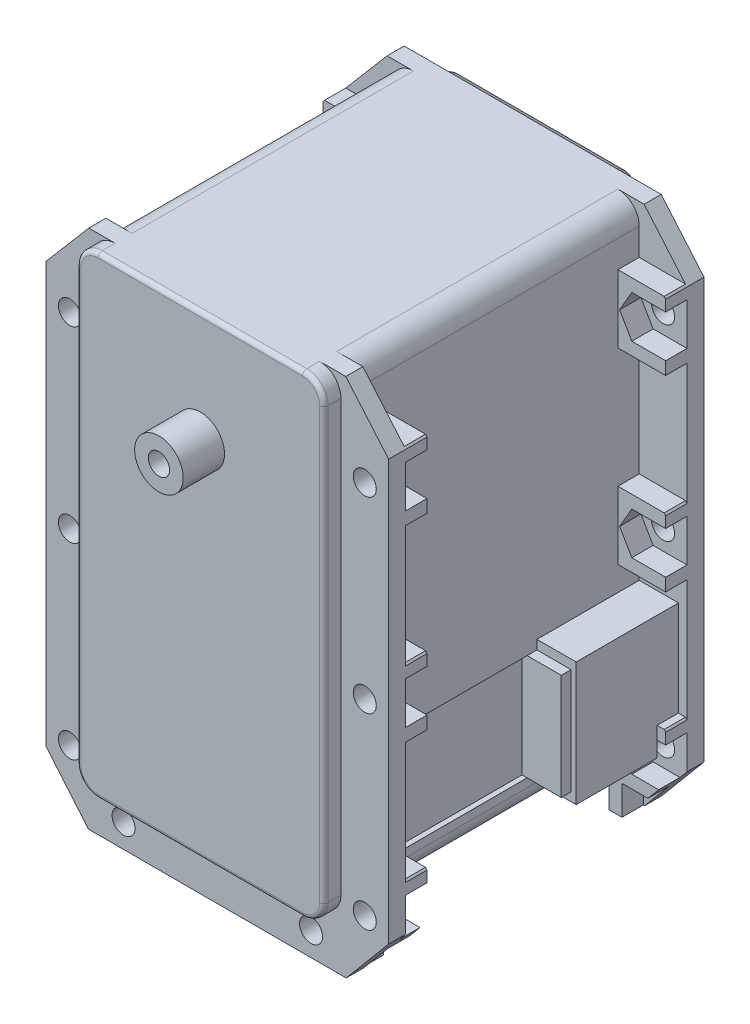
SolidWorks part; units mm, degrees
ref_plane "Ön Düzlem" through (0, 0, 0) normal (0, 0, 1) x (1, 0, 0)
ref_plane "Üst Düzlem" through (0, 0, 0) normal (0, 1, 0) x (1, 0, 0)
ref_plane "Sağ Düzlem" through (0, 0, 0) normal (1, 0, 0) x (0, 0, -1)
sketch "Sketch1" plane through (0, 0, 0) normal (0, 0, 1) x (1, 0, 0)
  line L1 (-14.5, 27.75) -> (14.5, 27.75)
  line L2 (-14.5, 27.75) -> (-14.5, -27.75)
  line L3 (-14.5, -27.75) -> (14.5, -27.75)
  line L4 (14.5, 27.75) -> (14.5, -27.75)
  line L5 (-14.5, 27.75) -> (14.5, -27.75) construction
  line L6 (-14.5, -27.75) -> (14.5, 27.75) construction
  point P0 (0, 0)
  dimension "D1" = 55.5
  dimension "D2" = 29
extrude "Boss-Extrude1" add sketch "Sketch1" along normal mid plane 41
ref_plane "Plane1" through (0, 0, 18.5) normal (0, 0, 1) x (1, 0, 0)
sketch "Sketch2" plane through (0, 0, 18.5) normal (0, 0, 1) x (1, 0, 0)
  line L1 (-15.0753, 27.75) -> (-20.1, 21.8536)
  line L2 (-20.1, 21.8536) -> (-20.1, -27.4155)
  line L3 (-20.1, -27.4155) -> (-15.1203, -33.35)
  line L4 (-15.1203, -33.35) -> (15.1203, -33.35)
  line L5 (15.1203, -33.35) -> (20.1, -27.4155)
  line L6 (20.1, -27.4155) -> (20.1, 21.8536)
  line L7 (20.1, 21.8536) -> (15.0753, 27.75)
  line L8 (15.0753, 27.75) -> (-15.0753, 27.75)
  line L9 (0, 0) -> (0, -33.35) construction
  line L10 (14.5, -27.75) -> (14.5, 27.75) construction
  line L11 (-14.5, -27.75) -> (14.5, -27.75) construction
  line L14 (14.5, 27.75) -> (-14.5, 27.75) construction
  circle A0 centre (17.3, 18.0845) radius 1.35
  circle A1 centre (17.3, -3.9155) radius 1.35
  circle A2 centre (17.3, -25.9155) radius 1.35
  circle A3 centre (11, -30.55) radius 1.35
  circle A4 centre (-11, -30.55) radius 1.35
  circle A5 centre (-17.3, -25.9155) radius 1.35
  circle A6 centre (-17.3, 18.0845) radius 1.35
  circle A7 centre (-17.3, -3.9155) radius 1.35
  dimension "D9" = 17.3
  dimension "D8" = 2.7
  dimension "D1" = 40.2
  dimension "D2" = 220
  dimension "D3" = 5.9345
  dimension "D4" = 5.6
  dimension "D5" = 22
  dimension "D6" = 22
  dimension "D7" = 220.437
  dimension "D10" = 11
  dimension "D11" = 1.5
  dimension "D12" = 2.8
extrude "Boss-Extrude2" add sketch "Sketch2" against normal blind 2 separate body
sketch "Sketch4" plane through (0, 0, 16.5) normal (0, 0, -1) x (-1, 0, 0)
  line L0 (14.5, 27.75) -> (14.5, -27.75) construction
  line L1 (20.1, 14.1095) -> (14.5, 14.1095)
  line L2 (20.1, 14.1095) -> (20.1, 22.0595)
  line L3 (20.1, 22.0595) -> (14.5, 22.0595)
  line L4 (14.5, 14.1095) -> (14.5, 22.0595)
  line L5 (20.1, 14.1095) -> (14.5, 22.0595) construction
  line L6 (20.1, 22.0595) -> (14.5, 14.1095) construction
  line L7 (20.1, 20.5595) -> (16.13, 20.5595)
  line L8 (16.13, 20.5595) -> (14.7, 18.0845)
  line L9 (14.7, 18.0845) -> (16.13, 15.6095)
  line L10 (16.13, 15.6095) -> (20.1, 15.6095)
  line L11 (17.3, 18.0845) -> (20.1, 18.0845) construction
  point P0 (17.3, 18.0845)
  point P6 (17.3, 18.0845)
  line M16 (20.1, -27.4155) -> (20.1, 21.8536)
  line M17 (20.1, 21.8536) -> (15.0753, 27.75)
  dimension "D1" = 7.95
  dimension "D2" = 4.95
  dimension "D3" = 1.43
  dimension "D4" = 0.2
extrude "Boss-Extrude6" add sketch "Sketch4" along normal blind 2.5 contours L10 L9 L8 L7 L2 L3 L4 L1 M17 M16 region at (-17.3, 14.2068, 16.5)
pattern_linear "LPattern1" count 3 spacing 22 along (0, -1, 0) of "Boss-Extrude6"
sketch "Sketch6" plane through (0, 0, 16.5) normal (0, 0, -1) x (-1, 0, 0)
  line L0 (15.1203, -33.35) -> (-15.1203, -33.35) construction
  line L1 (14.975, -27.75) -> (7.025, -27.75)
  line L2 (14.975, -27.75) -> (14.975, -33.35)
  line L3 (14.975, -33.35) -> (7.025, -33.35)
  line L4 (7.025, -27.75) -> (7.025, -33.35)
  line L5 (14.975, -27.75) -> (7.025, -33.35) construction
  line L6 (14.975, -33.35) -> (7.025, -27.75) construction
  line L7 (13.475, -33.35) -> (13.475, -29.38)
  line L8 (13.475, -29.38) -> (11, -27.95)
  line L9 (11, -27.95) -> (8.525, -29.38)
  line L10 (8.525, -29.38) -> (8.525, -33.35)
  line L11 (11, -30.55) -> (11, -33.35) construction
  point P0 (11, -30.55)
  line M6 (18.0232, -29.8905) -> (14.5, -29.8905)
  line M7 (14.5, -29.8905) -> (14.5, -21.9405)
  line M14 (-15.1203, -33.35) -> (15.1203, -33.35)
  dimension "D1" = 7.95
  dimension "D2" = 4.95
  dimension "D3" = 0.2
  dimension "D4" = 1.43
extrude "Boss-Extrude7" add sketch "Sketch6" along normal up to surface (2.5 mm away) contours L2 L1 M7 M6 | L10 L9 L8 L7 L3 L2 L1 L4 M6 M7 M14 region at (-14.7375, -28.8202, 16.5) region at (-14.4028, -28.8202, 16.5)
mirror "Mirror1" about plane through (0, 0, 0) normal (1, 0, 0) of "Boss-Extrude6", "LPattern1", "Boss-Extrude7"
sketch "Sketch7" plane through (0, 0, 18.5) normal (0, 0, 1) x (1, 0, 0)
  line L0 (15.0753, 27.75) -> (24.5744, 27.75)
  line L1 (24.5744, 27.75) -> (23.5636, -35.3493)
  line L2 (23.5636, -35.3493) -> (-23.3668, -35.3493)
  line L3 (-23.3668, -35.3493) -> (-23.3668, 27.75)
  line L4 (-23.3668, 27.75) -> (-15.0753, 27.75)
  line L8 (15.0753, 27.75) -> (-15.0753, 27.75)
  line L9 (-15.0753, 27.75) -> (-20.1, 21.8536)
  line L10 (-20.1, 21.8536) -> (-20.1, -27.4155)
  line L11 (-20.1, -27.4155) -> (-15.1203, -33.35)
  line L12 (-15.1203, -33.35) -> (15.1203, -33.35)
  line L13 (15.1203, -33.35) -> (20.1, -27.4155)
  line L14 (20.1, -27.4155) -> (20.1, 21.8536)
  line L15 (20.1, 21.8536) -> (15.0753, 27.75)
  line L16 (15.0753, 27.75) -> (-15.0753, 27.75)
  line L17 (-15.0753, 27.75) -> (-20.1, 21.8536)
  line L18 (-20.1, 21.8536) -> (-20.1, -27.4155)
  line L19 (-20.1, -27.4155) -> (-15.1203, -33.35)
  line L20 (-15.1203, -33.35) -> (15.1203, -33.35)
  line L21 (15.1203, -33.35) -> (20.1, -27.4155)
  line L22 (20.1, -27.4155) -> (20.1, 21.8536)
  line L23 (20.1, 21.8536) -> (15.0753, 27.75)
  line M18 (-15.0753, 27.75) -> (-20.1, 21.8536)
  line M19 (-20.1, 21.8536) -> (-20.1, -27.4155)
  line M20 (-20.1, -27.4155) -> (-15.1203, -33.35)
  line M21 (-15.1203, -33.35) -> (15.1203, -33.35)
  line M22 (15.1203, -33.35) -> (20.1, -27.4155)
  line M23 (20.1, -27.4155) -> (20.1, 21.8536)
  line M24 (20.1, 21.8536) -> (15.0753, 27.75)
  dimension "D1" = 0
extrude "Cut-Extrude1" cut sketch "Sketch7" against normal through all contours L4 L3 L2 L1 L0 M24 M23 M22 M21 M20 M19 M18 region at (19.8248, 26.9575, 18.5)
mirror "Mirror2" about plane through (0, 0, 0) normal (0, 0, 1) of bodies 108
sketch "Sketch8" plane through (0, 0, 20.5) normal (0, 0, 1) x (1, 0, 0)
  line L0 (14.5, 27.75) -> (-14.5, 27.75) construction
  circle A0 centre (0, 14.75) radius 2.85
  dimension "D1" = 5.7
  dimension "D2" = 13
extrude "Boss-Extrude8" add sketch "Sketch8" along normal blind 4.85
fillet "Fillet1" radius 2.5 4 edges at (14.5, 27.75, 0) (-14.5, 27.75, 0) (-14.5, -27.75, 0) (14.5, -27.75, 0)
ref_plane "Plane2" through (0, 14.75, 0) normal (0, 1, 0) x (1, 0, 0)
sketch "Sketch11" plane through (0, 14.75, 0) normal (0, 1, 0) x (1, 0, 0)
  line L0 (0, 0) -> (0, 28.343) construction
  line L2 (3.3693, 19.5) -> (0, 19.5)
  line L3 (3.3693, 19.5) -> (4, 19.5)
  line L4 (4, 19.5) -> (4, 19.2)
  line L5 (4, 19.2) -> (6.5, 19.2)
  line L6 (6.5, 19.2) -> (6.5, 22)
  line L7 (6.5, 22) -> (0, 22)
  line L8 (0, 19.5) -> (0, 22)
  line L11 (12, 20.5) -> (-12, 20.5) construction
  dimension "D1" = 1.5
  dimension "D2" = 1.3
  dimension "D3" = 0.3
  dimension "D4" = 6.5
  dimension "D5" = 4
revolve "Cut-Revolve1" cut sketch "Sketch11" angle 360 about L0
sketch "Sketch12" plane through (0, 0, -19.5) normal (0, 0, -1) x (-1, 0, 0)
  circle A0 centre (0, 14.75) radius 3
  circle A1 centre (0, 14.75) radius 4 construction
  circle A2 centre (0, 14.75) radius 1.6
  dimension "D1" = 6
  dimension "D2" = 3.2
extrude "Boss-Extrude10" add sketch "Sketch12" along normal offset from surface (2.5 mm away) 1.5 up to face at (6.5, 14.75, -20.5) offset beyond the face yes
combine bodies "Combine1" operation type add bodies to combine 113 108 109
sketch "Sketch13" plane through (0, 0, -20.5) normal (0, 0, -1) x (-1, 0, 0)
  line L2 (-13.7678, 27.0178) -> (0, 14.75) construction
  line L3 (-12.2619, 23.6759) -> (-14.5, 23.6759)
  line L4 (-14.5, -25.25) -> (-14.5, 25.25) construction
  line L5 (-10.2619, 28.327) -> (-10.2619, 25.6759)
  line L6 (-14.5, 28.327) -> (-10.2619, 28.327)
  line L7 (-14.5, 23.6759) -> (-14.5, 28.327)
  circle A0 centre (-12.2619, 25.6759) radius 2
  arc A1 (-12, 27.75) -> (-14.5, 25.25) centre (-12, 25.25) ccw construction
  line M2 (12, 27.75) -> (-12, 27.75)
  arc M3 (-12, 27.75) -> (-14.5, 25.25) centre (-12, 25.25) ccw
  line M4 (-14.5, 25.25) -> (-14.5, -25.25)
  dimension "D1" = 4
extrude "Cut-Extrude2" cut sketch "Sketch13" against normal up to surface (2 mm away) contours A0 L5 M2 M3 | A0 L2 | L2 A0 | L2 L3 A0 M3 M4 | L7 L5 L6 M3 M2 | L2 A0 M3 region at (13.6557, 27.1129, -20.5) region at (14.0361, 24.4903, -20.5) region at (12.9337, 27.7385, -20.5) region at (11.6972, 26.3097, -20.5) region at (12.8266, 25.0422, -20.5) region at (10.8265, 27.3078, -20.5) up to face at (-18.65, -3.9155, -18.5)
mirror "Mirror3" about plane through (0, 0, 0) normal (1, 0, 0) of "Cut-Extrude2"
mirror "Mirror4" about plane through (0, 0, 0) normal (0, 1, 0) of "Mirror3"
sketch "Sketch14" plane through (-14.5, 0, 0) normal (-1, 0, 0) x (0, 0, 1)
  line L0 (-20.5, 25.6759) -> (-20.5, 23.6759) construction
  line L1 (-20.5, 24.5877) -> (-20.5, 23.5276) construction
  line L2 (-20.5, 23.6759) -> (-20.5, -23.6759) construction
  line L3 (-18.5, 27.75) -> (-20.8698, 27.75)
  line L4 (-20.8698, 27.75) -> (-20.8698, 24.5877)
  line L5 (-20.8698, 24.5877) -> (-20.5, 24.5877)
  arc A0 (-20.5, 24.5877) -> (-18.5, 27.75) centre (-17, 24.5877) cw
  dimension "D1" = 3.5
extrude "Cut-Extrude3" cut sketch "Sketch14" against normal through all
sketch "Sketch15" plane through (-14.5, 0, 0) normal (-1, 0, 0) x (0, 0, 1)
  line L0 (-16.5, -7.8905) -> (-16.5, -22.1464) construction
  line L1 (-16.5, -11.83) -> (16.5, -11.83)
  line L2 (-16.5, -11.83) -> (-16.5, -24.25)
  line L3 (-16.5, -24.25) -> (16.5, -24.25)
  line L4 (16.5, -11.83) -> (16.5, -24.25)
  line L5 (-16.5, -11.83) -> (16.5, -24.25) construction
  line L6 (-16.5, -24.25) -> (16.5, -11.83) construction
  line L7 (16.5, -7.8905) -> (16.5, -22.1464) construction
  line L8 (-14, -25.25) -> (14, -25.25) construction
  point P0 (0, -18.04)
  dimension "D1" = 12.42
  dimension "D2" = 1
extrude "Cut-Extrude4" cut sketch "Sketch15" against normal blind 0.6
sketch "Sketch16" plane through (-13.9, 0, 0) normal (-1, 0, 0) x (0, 0, 1)
  line L0 (-16.5, -7.8905) -> (-16.5, -22.1464) construction
  line L1 (-16.5, -10.75) -> (-4.5, -10.75)
  line L2 (-16.5, -10.75) -> (-16.5, -25.25)
  line L3 (-16.5, -25.25) -> (-4.5, -25.25)
  line L4 (-4.5, -10.75) -> (-4.5, -25.25)
  line L5 (-16.5, -10.75) -> (-4.5, -25.25) construction
  line L6 (-16.5, -25.25) -> (-4.5, -10.75) construction
  line L8 (-14, -25.25) -> (14, -25.25) construction
  line L10 (-14, -25.25) -> (-14, -22.1464)
  line L11 (-14, -22.1464) -> (-16.5, -22.1464)
  point P0 (-10.5, -18)
  line M2 (16.5, -11.83) -> (-16.5, -11.83)
  line M3 (-16.5, -11.83) -> (-16.5, -24.25)
  line M4 (-16.5, -24.25) -> (16.5, -24.25)
  dimension "D1" = 14.5
  dimension "D2" = 12
extrude "Boss-Extrude11" add sketch "Sketch16" along normal offset from surface (5.2 mm away) 4.6 separate body contours L4 L1 L2 M2 | L10 L3 L4 M4 | L11 L10 L4 M4 M2 M3 region at (-13.9, -11.29, -10.5) region at (-13.9, -17.8513, -10.3263) region at (-13.9, -24.75, -9.25) up to face at (-14.5, 7.0096, 0) offset beyond the face yes
sketch "Sketch17" plane through (-13.9, 0, 0) normal (-1, 0, 0) x (0, 0, 1)
  line L0 (-16.5, -24.25) -> (16.5, -24.25) construction
  line L1 (-4.5, -11.83) -> (-3.35, -11.83)
  line L2 (-4.5, -11.83) -> (-4.5, -24.25)
  line L3 (-4.5, -24.25) -> (-3.35, -24.25)
  line L4 (-3.35, -11.83) -> (-3.35, -24.25)
  line L5 (-4.5, -11.83) -> (-3.35, -24.25) construction
  line L6 (-4.5, -24.25) -> (-3.35, -11.83) construction
  line L7 (16.5, -11.83) -> (-16.5, -11.83) construction
  line L9 (-16.5, -7.8905) -> (-16.5, -22.1464) construction
  point P0 (-3.925, -18.04)
  dimension "D1" = 1.15
  dimension "D2" = 12
extrude "Boss-Extrude12" add sketch "Sketch17" along normal blind 4.6
mirror "Mirror11" about plane through (0, 0, 0) normal (1, 0, 0) of "Cut-Extrude4"
mirror "Mirror10" about plane through (0, 0, 0) normal (1, 0, 0) of bodies 121
combine bodies "Combine2" operation type add bodies to combine 124 123 121
fillet "Fillet3" radius 1.5 6 edges at (-14.5, 23.6759, -19.5) (14.5, 23.6759, -19.5) (10.2619, -27.75, -19.5) (14.5, -23.6759, -19.5) (-14.5, -23.6759, -19.5) (-10.2619, -27.75, -19.5)
fillet "Fillet4" radius 0.5 31 edges at (14.5, 0, 20.5) (13.7678, -27.0178, 20.5) (0, -27.75, 20.5) (-13.7678, -27.0178, 20.5) (-14.5, 0, 20.5) (-13.7678, 27.0178, 20.5) (0, 27.75, 20.5) (-10.2619, 26.9009, -19.6266) (-10.3357, 25.1376, -20.4565) (-11.307, 23.9186, -20.5) (-12.6309, 23.6759, -20.5) (-14.0607, 23.2366, -20.5) (10.2619, 26.9009, -19.6266) (10.3357, 25.1376, -20.4565) (11.307, 23.9186, -20.5) (12.6309, 23.6759, -20.5) (14.0607, 23.2366, -20.5) (14.5, 0, -20.5) (14.0607, -23.2366, -20.5) (12.6309, -23.6759, -20.5) (10.8477, -24.2617, -20.5) (10.2619, -25.963, -20.5) (9.8225, -27.3107, -20.5) (0, -27.75, -20.5) (-9.8225, -27.3107, -20.5) (-10.2619, -25.963, -20.5) (-10.8477, -24.2617, -20.5) (-12.6309, -23.6759, -20.5) (-14.0607, -23.2366, -20.5) (13.7678, 27.0178, 20.5) (-14.5, 0, -20.5)
sketch "Sketch18" plane through (0, 0, 25.35) normal (0, 0, 1) x (1, 0, 0)
  circle A0 centre (0, 14.75) radius 1.25
  dimension "D1" = 2.5
extrude "Cut-Extrude5" cut sketch "Sketch18" against normal blind 10
